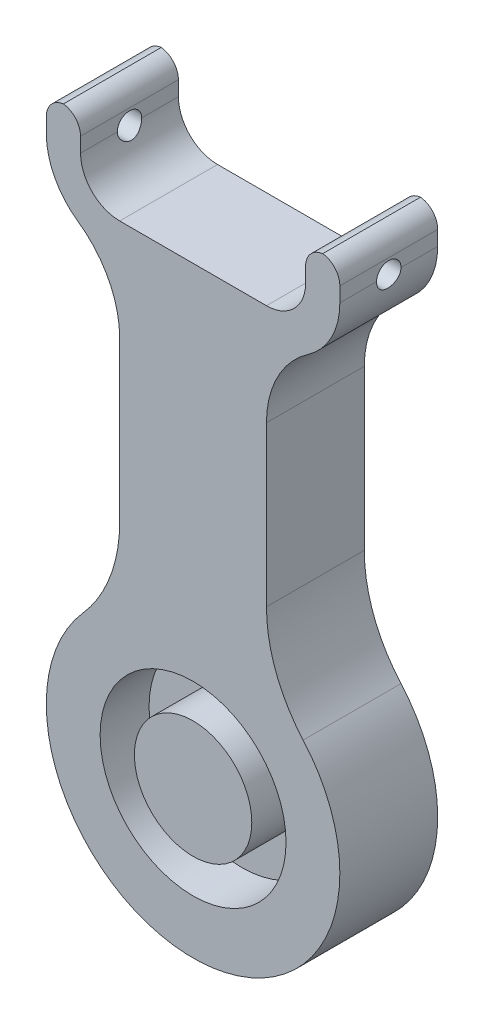
SolidWorks part; units mm, degrees
ref_plane "Front Plane" through (0, 0, 0) normal (0, 0, 1) x (1, 0, 0)
ref_plane "Top Plane" through (0, 0, 0) normal (0, 1, 0) x (1, 0, 0)
ref_plane "Right Plane" through (0, 0, 0) normal (1, 0, 0) x (0, 0, -1)
sketch "Sketch1" plane through (0, 0, 0) normal (0, 0, 1) x (1, 0, 0)
  circle A0 centre (0, 0) radius 15
  circle A1 centre (0, 0) radius 3
  dimension "D1" = 6
  dimension "D2" = 30
extrude "Boss-Extrude1" add sketch "Sketch1" along normal blind 10
sketch "Sketch2" plane through (0, 0, 0) normal (0, 0, 1) x (1, 0, 0)
  line L1 (-7.5, 12.9904) -> (7.5, 12.9904)
  line L2 (-7.5, 12.9904) -> (-7.5, 42.9904)
  line L3 (-7.5, 42.9904) -> (7.5, 42.9904)
  line L4 (7.5, 12.9904) -> (7.5, 42.9904)
  circle A0 centre (0, 0) radius 15 construction
  dimension "D1" = 15
  dimension "D2" = 30
extrude "Boss-Extrude2" add sketch "Sketch2" along normal up to surface (10 mm away) up to face at (15, 0, 10)
fillet "Fillet1" radius 15 2 edges at (-7.5, 12.9904, 5) (7.5, 12.9904, 5)
sketch "Sketch5" plane through (0, 0, 0) normal (0, 0, -1) x (-1, 0, 0)
  line L1 (-5, 3.5) -> (5, 3.5)
  line L2 (-5, 3.5) -> (-5, 1.5)
  line L3 (-5, 1.5) -> (5, 1.5)
  line L4 (5, 3.5) -> (5, 1.5)
  circle A0 centre (0, 0) radius 3 construction
  dimension "D1" = 1.5
  dimension "D2" = 2
  dimension "D3" = 10
  dimension "D4" = 5
extrude "Boss-Extrude3" add sketch "Sketch5" against normal blind 10
sketch "Sketch7" plane through (0, 0, 10) normal (0, 0, 1) x (1, 0, 0)
  circle A0 centre (0, 0) radius 3
extrude "Boss-Extrude4" add sketch "Sketch7" against normal blind 3
chamfer "Chamfer1" distance 0.7 angle 45 2 edges at (0, -3, 7) (0, 1.5, 7)
sketch "Sketch9" plane through (0, 0, 0) normal (0, 0, -1) x (-1, 0, 0)
  line L0 (-7.5, 42.9904) -> (7.5, 42.9904) construction
  line L1 (-7.5, 19.8431) -> (-7.5, 42.9904) construction
  line L3 (-15, 50.4904) -> (-15, 53.9904)
  line L4 (-15, 53.9904) -> (-11.5, 53.9904)
  line L5 (-11.5, 53.9904) -> (-11.5, 50.4904)
  line L6 (-7.5, 46.4904) -> (7.5, 46.4904)
  line L7 (0, 46.4904) -> (0, 42.9904)
  line L8 (7.5, 42.9904) -> (-7.5, 42.9904)
  line L9 (0, 62.4917) -> (0, 38.0275) construction
  line L10 (11.5, 53.9904) -> (11.5, 50.4904)
  line L11 (15, 53.9904) -> (11.5, 53.9904)
  line L12 (15, 50.4904) -> (15, 53.9904)
  arc A0 (-15, 50.4904) -> (-7.5, 42.9904) centre (-7.5, 50.4904) ccw
  arc A2 (-11.5, 50.4904) -> (-7.5, 46.4904) centre (-7.5, 50.4904) ccw
  arc A3 (11.5, 50.4904) -> (7.5, 46.4904) centre (7.5, 50.4904) cw
  arc A4 (15, 50.4904) -> (7.5, 42.9904) centre (7.5, 50.4904) cw
  line M23 (7.5, 42.9904) -> (-7.5, 42.9904)
  dimension "D1" = 3.5
  dimension "12.5" = 15
  dimension "D2" = 7.5
  dimension "D3" = 0
  dimension "D7" = 3.5
  dimension "D8" = 0
extrude "Boss-Extrude6" add sketch "Sketch9" against normal blind 10 contours A2 L5 L4 L3 A0 L7 L6 M23 | A4 L12 L11 L10 A3 L6 L7 M23 region at (14.814, 52.2404, 0) region at (-0.186, 44.7404, 0)
fillet "Fillet4" radius 2 4 edges at (11.5, 53.9904, 5) (15, 53.9904, 5) (-11.5, 53.9904, 5) (-15, 53.9904, 5)
fillet "Fillet2" radius 10 2 edges at (-7.5, 42.9904, 5) (7.5, 42.9904, 5)
sketch "Sketch10" plane through (15, 0, 0) normal (1, 0, 0) x (0, 0, -1)
  line L0 (-10, 50.4904) -> (0, 50.4904) construction
  line L1 (0, 44.3355) -> (0, 50.4904) construction
  circle A0 centre (-5, 50.4904) radius 1.25
  dimension "D3" = 2.5
  dimension "D1" = 0
  dimension "D2" = 5
extrude "Cut-Extrude1" cut sketch "Sketch10" against normal through all both and the other way through all
sketch "Sketch11" plane through (0, 0, 10) normal (0, 0, 1) x (1, 0, 0)
  circle A0 centre (0, 0) radius 9.5
  circle A1 centre (0, 0) radius 6
  dimension "D1" = 19
  dimension "D2" = 12
extrude "Cut-Extrude2" cut sketch "Sketch11" against normal blind 5
